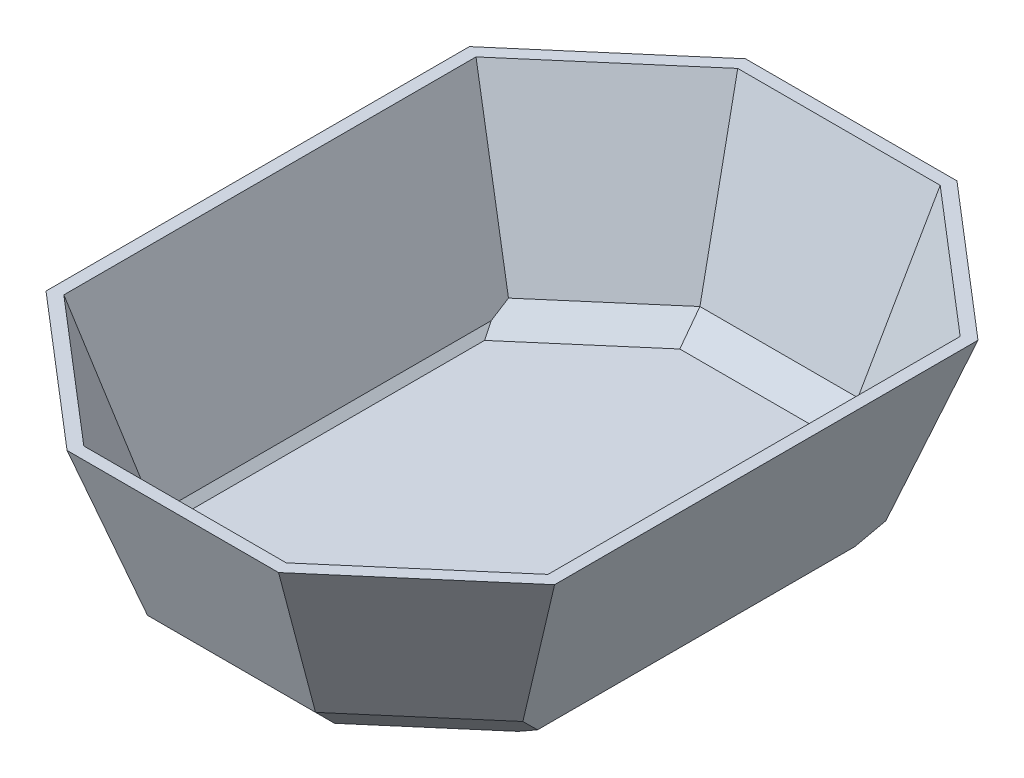
SolidWorks part; units mm, degrees
note: '?' marks a value the reader was unsure of.
ref_plane "Front Plane" through (0, 0, 0) normal (0, 0, 1) x (1, 0, 0)
ref_plane "Top Plane" through (0, 0, 0) normal (0, 1, 0) x (1, 0, 0)
ref_plane "Right Plane" through (0, 0, 0) normal (1, 0, 0) x (0, 0, -1)
ref_axis "X" through (-88.99, 0, 0) along (1, 0, 0)?
ref_axis "Y" through (0, 55, 0) along (0, -1, 0)?
ref_axis "Z" through (0, 0, -88.99) along (0, 0, 1)?
sketch "Sketch1" plane through (0, 0, 0) normal (0, 1, 0) x (1, 0, 0)
  line L0 (-48.2247, 46.933) -> (-20.883, 70.3995)
  line L1 (-48.2247, 46.933) -> (48.2247, 46.933)
  line L2 (-48.2247, 46.933) -> (-48.2247, -46.933)
  line L3 (-48.2247, -46.933) -> (48.2247, -46.933)
  line L4 (48.2247, 46.933) -> (48.2247, -46.933)
  line L5 (-48.2247, 46.933) -> (48.2247, -46.933) construction
  line L6 (-48.2247, -46.933) -> (48.2247, 46.933) construction
  line L7 (-20.883, 70.3995) -> (20.883, 70.3995)
  line L8 (20.883, 70.3995) -> (48.2247, 46.933)
  line L9 (0, 70.3995) -> (0, 46.933) construction
  line L10 (-48.2247, 0) -> (0, 0) construction
  line L11 (20.883, -70.3995) -> (48.2247, -46.933)
  line L12 (-20.883, -70.3995) -> (20.883, -70.3995)
  line L13 (-48.2247, -46.933) -> (-20.883, -70.3995)
  point P0 (0, 0)
extrude "Boss-Extrude1" add sketch "Sketch1" along normal blind 50 contours L4 L1 L2 L3 | L8 L7 L0 L1 | L3 L13 L12 L11
draft "Draft1" type of draft neutral plane draft angle 20 faces to draft 8 face at (-34.5539, 25, 58.6663) face at (-48.2247, 25, 0) face at (-34.5539, 25, -58.6663) face at (0, 25, -70.3995) face at (34.5539, 25, -58.6663) face at (48.2247, 25, 0) face at (34.5539, 25, 58.6663) face at (0, 25, 70.3995) neutral plane through (0, 0, 0) neutral plane normal (0, -1, 0) parameters "D1"=20
chamfer "Chamfer1" distance 5 angle 45 6 edges at (34.5539, 0, -58.6663) (0, 0, -70.3995) (-34.5539, 0, -58.6663) (-34.5539, 0, 58.6663) (0, 0, 70.3995) (34.5539, 0, 58.6663)
chamfer "Chamfer2" distance 2 angle 45 2 edges at (-48.2247, 0, 2.2177) (48.2247, 0, 2.2177)
shell "Shell1" thickness 3
